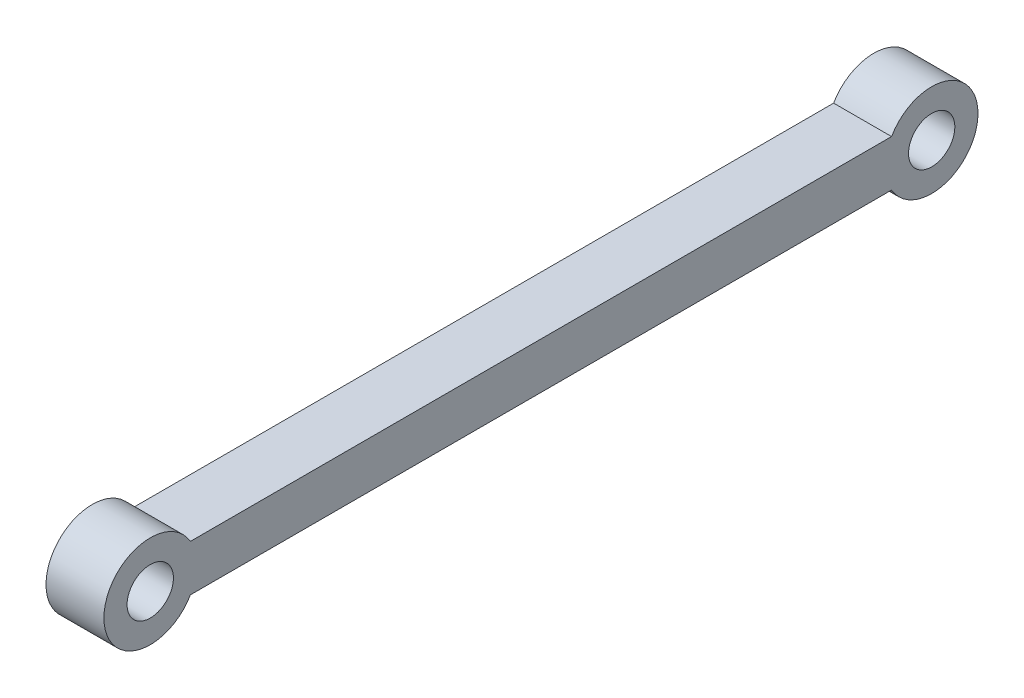
SolidWorks part; units mm, degrees
ref_plane "Front Plane" through (0, 0, 0) normal (0, 0, 1) x (1, 0, 0)
ref_plane "Top Plane" through (0, 0, 0) normal (0, 1, 0) x (1, 0, 0)
ref_plane "Right Plane" through (0, 0, 0) normal (1, 0, 0) x (0, 0, -1)
sketch "Sketch1" plane through (0, 0, 0) normal (1, 0, 0) x (0, 0, -1)
  line L0 (-15.1339, 1) -> (15.1339, 1)
  line L5 (-15.1339, -1) -> (15.1339, -1)
  line L6 (0, 1) -> (0, -1) construction
  circle A1 centre (-16.866, 0) radius 1
  arc A2 (-15.1339, 1) -> (-15.1339, -1) centre (-16.866, 0) ccw
  circle A4 centre (16.866, 0) radius 1
  arc A5 (15.1339, -1) -> (15.1339, 1) centre (16.866, 0) ccw
  point P0 (0, 0)
  point P11 (0, 1)
  point P13 (0, -1)
  point P16 (0, 0)
  dimension "D1" = 2
  dimension "D2" = 4
  dimension "D3" = 33.732
  dimension "D4" = 2
extrude "Boss-Extrude1" add sketch "Sketch1" along normal mid plane 2.5
